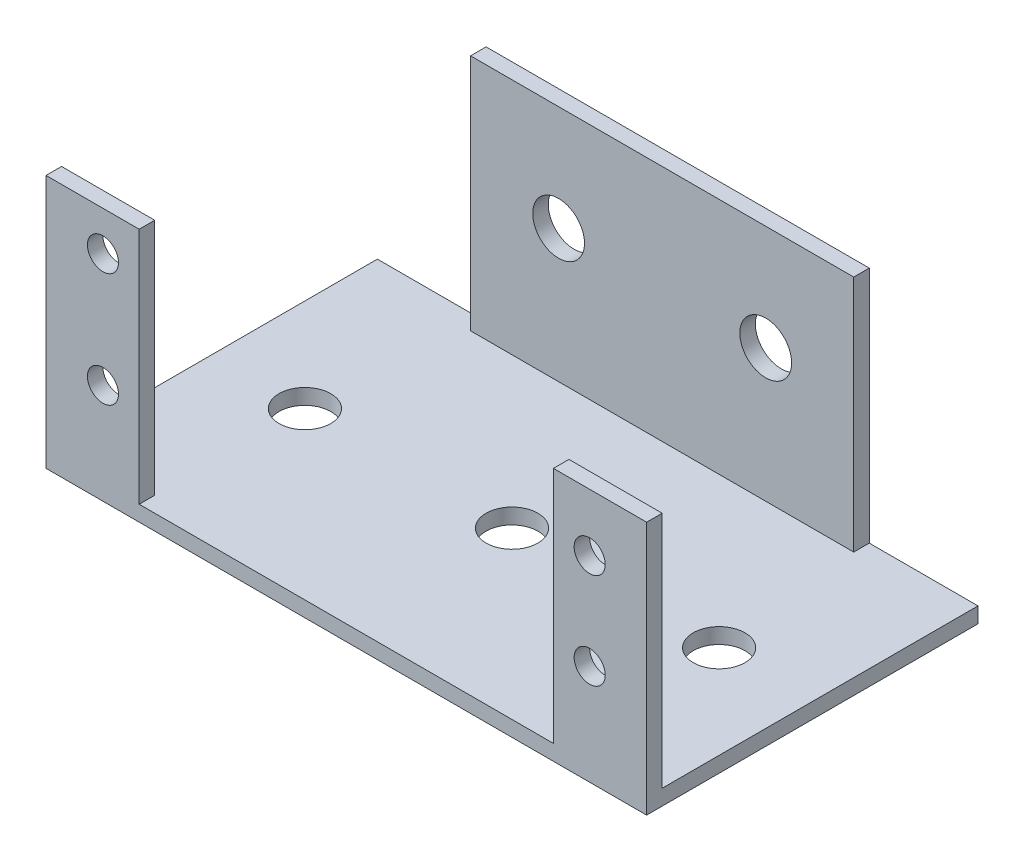
SolidWorks part; units mm, degrees
ref_plane "Front Plane" through (0, 0, 0) normal (0, 0, 1) x (1, 0, 0)
ref_plane "Top Plane" through (0, 0, 0) normal (0, 1, 0) x (1, 0, 0)
ref_plane "Right Plane" through (0, 0, 0) normal (1, 0, 0) x (0, 0, -1)
sketch "Sketch1" plane through (0, 0, 0) normal (0, 1, 0) x (1, 0, 0)
  line L0 (-29, -14.5) -> (29, -14.5)
  line L1 (29, 16) -> (-29, 16)
  line L2 (29, 16) -> (29, -16)
  line L3 (29, -16) -> (-29, -16)
  line L4 (-29, 16) -> (-29, -16)
  line L5 (29, 16) -> (-29, -16) construction
  line L6 (29, -16) -> (-29, 16) construction
  line L7 (-20, -14.5) -> (-20, -16)
  line L8 (20, -14.5) -> (20, -16)
  line L10 (18.5, 16) -> (-18.5, 16)
  line L11 (18.5, 16) -> (18.5, 14.5)
  line L12 (18.5, 14.5) -> (-18.5, 14.5)
  line L13 (-18.5, 16) -> (-18.5, 14.5)
  circle A0 centre (-20, 0) radius 2.5
  circle A1 centre (20, 0) radius 2.5
  circle A2 centre (0, 0) radius 2.5
  point P0 (0, 0)
  point P16 (0, -14.5)
  point P21 (0, 14.5)
  dimension "D4" = 5
  dimension "D1" = 58
  dimension "D2" = 32
  dimension "D3" = 1.5
  dimension "D5" = 20
  dimension "D6" = 20
  dimension "D7" = 40
  dimension "D8" = 20
  dimension "D9" = 37
  dimension "D10" = 1.5
extrude "Boss-Extrude1" add sketch "Sketch1" against normal blind 1.5 contours L1 L4 L0 L2 A1 A0 | L0 L4 L3 L2 | L1 L13 L12 L11 | A0 | A1 | L2 L1 L4 L3 region at (-28.3447, 0, -0.75) region at (0, 0, -15.25) region at (-20, 0, 0) region at (20, 0, 0)
extrude "Boss-Extrude2" add sketch "Sketch1<3>" along normal blind 23 contours L7 L0 L4 L3 | L0 L8 L3 L2 region at (-24.5, 0, 15.25) region at (24.5, 0, 15.25)
sketch "Sketch1<3>" plane through (0, 0, 0) normal (0, 1, 0) x (1, 0, 0) same geometry as "Sketch1"
sketch "Sketch2" plane through (0, 0, 16) normal (0, 0, 1) x (1, 0, 0)
  circle A0 centre (-23.5, 19.1975) radius 1.5
  circle A1 centre (-23.5, 8.1975) radius 1.5
  circle A2 centre (23.5, 17.4466) radius 1.5
  circle A3 centre (23.5, 8.1975) radius 1.5
  dimension "D4" = 3
  dimension "D1" = 11
  dimension "D2" = 47
  dimension "D3" = 23.5
extrude "Cut-Extrude1" cut sketch "Sketch2" against normal through all
extrude "Boss-Extrude3" add sketch "Sketch1<4>" along normal blind 23 contours L1 L13 L12 L11 region at (0, 0, -15.25)
sketch "Sketch1<4>" plane through (0, 0, 0) normal (0, 1, 0) x (1, 0, 0) same geometry as "Sketch1"
sketch "Sketch3" plane through (0, 0, -14.5) normal (0, 0, 1) x (1, 0, 0)
  line L0 (23.5, 17.4466) -> (23.5, 8.1975) construction
  line L1 (0, 0) -> (0, 29.7064) construction
  circle A0 centre (10, 12.822) radius 2.5
  circle A1 centre (23.5, 17.4466) radius 1.5 construction
  circle A2 centre (-10, 12.822) radius 2.5
  point P9 (23.5, 12.822)
  dimension "D1" = 13.5
  dimension "D2" = 5
extrude "Cut-Extrude2" cut sketch "Sketch3" against normal through all
extrude "Cut-Extrude3" cut sketch "Sketch1<5>" against normal blind 25 contours A1 | A2 | A0 region at (20, 0, 0) region at (0, 0, 0)
sketch "Sketch1<5>" plane through (0, 0, 0) normal (0, 1, 0) x (1, 0, 0) same geometry as "Sketch1"
